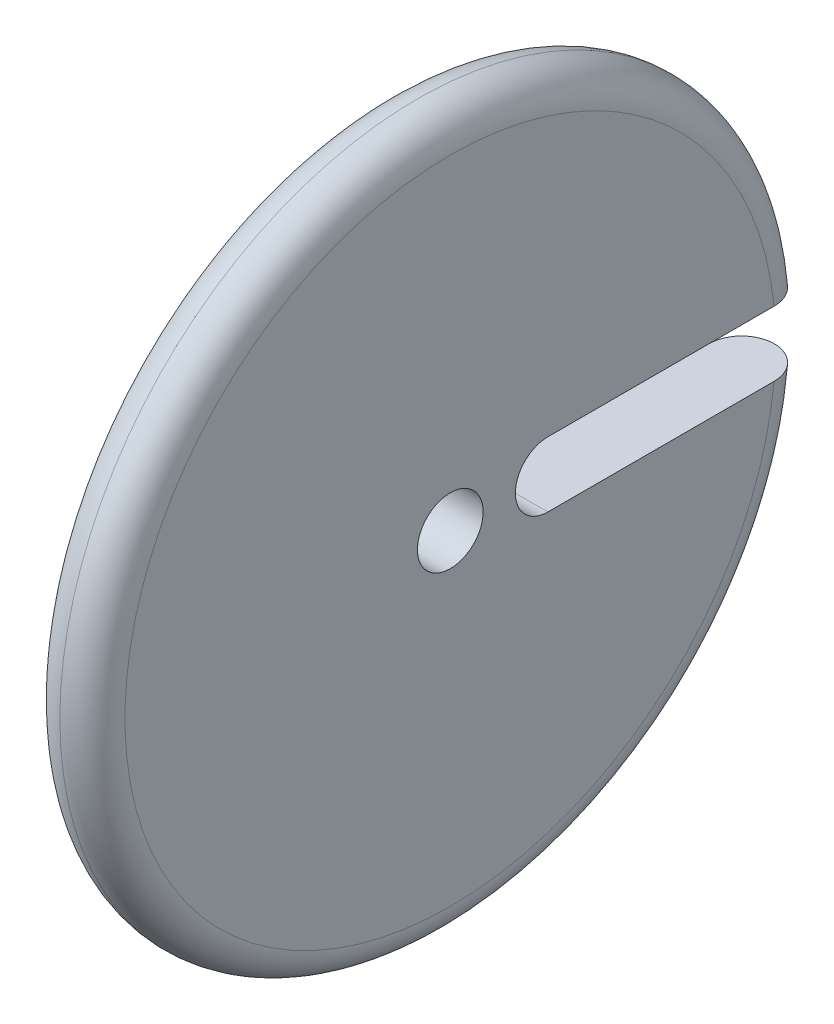
SolidWorks part; units mm, degrees
ref_plane "Front Plane" through (0, 0, 0) normal (0, 0, 1) x (1, 0, 0)
ref_plane "Top Plane" through (0, 0, 0) normal (0, 1, 0) x (1, 0, 0)
ref_plane "Right Plane" through (0, 0, 0) normal (1, 0, 0) x (0, 0, -1)
sketch "Sketch1" plane through (0, 0, 0) normal (1, 0, 0) x (0, 0, -1)
  circle A1 centre (0, 0) radius 110
  dimension "D1" = 220
extrude "Boss-Extrude1" add sketch "Sketch1" along normal blind 20 contours A1
sketch "Sketch2" plane through (0, 0, 0) normal (1, 0, 0) x (0, 0, -1)
  circle A0 centre (0, 0) radius 10.1
  dimension "D1" = 20.2
sketch "Sketch3" plane through (0, 0, 0) normal (1, 0, 0) x (0, 0, -1)
  line L0 (30, 0) -> (113.4922, 0) construction
  line L2 (113.4922, 0) -> (30, 0) construction
  line L3 (113.4922, -10) -> (30, -10)
  line L4 (113.4922, 10) -> (30, 10)
  line L6 (33, 0) -> (-33, 0) construction
  arc A2 (113.4922, -10) -> (113.4922, 10) centre (113.4922, 0) ccw
  arc A3 (30, 10) -> (30, -10) centre (30, 0) ccw
  point P6 (71.7461, 0)
extrude "Cut-Extrude2" cut sketch "Sketch3" along normal blind 20
extrude "Cut-Extrude3" cut sketch "Sketch2" along normal blind 20 contours A0
fillet "Fillet1" radius 10 2 edges at (20, 0, 110) (0, 0, 110)
scale "Scale1" scale about origin uniform scaling yes scale factor 0.5
